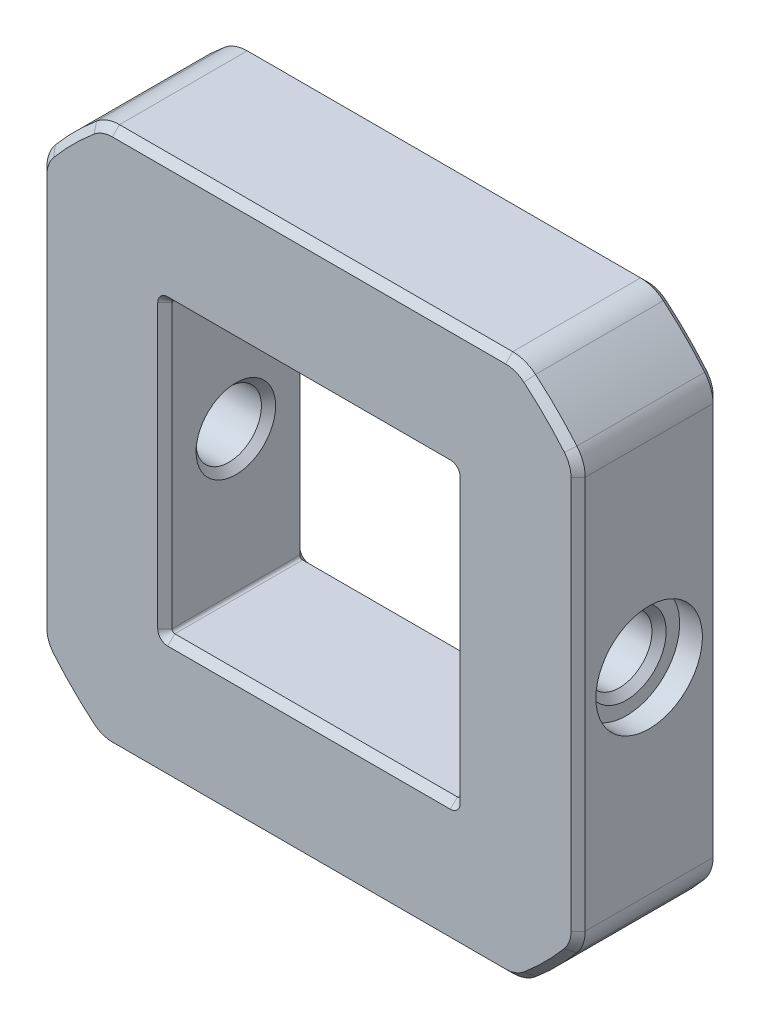
SolidWorks part; units mm, degrees
ref_plane "Front" through (0, 0, 0) normal (0, 0, 1) x (1, 0, 0)
ref_plane "Top" through (0, 0, 0) normal (0, 1, 0) x (1, 0, 0)
ref_plane "Right" through (0, 0, 0) normal (1, 0, 0) x (0, 0, -1)
sketch "Skizze1" plane through (0, 0, 0) normal (0, 0, 1) x (1, 0, 0)
  line L0 (14.7274, 18.95) -> (-14.7274, 18.95)
  line L1 (-10.15, -10.15) -> (10.15, -10.15)
  line L2 (-10.15, -10.15) -> (-10.15, 10.15)
  line L3 (-10.15, 10.15) -> (10.15, 10.15)
  line L4 (10.15, -10.15) -> (10.15, 10.15)
  line L5 (-10.15, -10.15) -> (10.15, 10.15) construction
  line L6 (-10.15, 10.15) -> (10.15, -10.15) construction
  line L7 (18.95, 14.7274) -> (18.95, -14.7274)
  line L8 (-14.7274, -18.95) -> (14.7274, -18.95)
  line L9 (-18.95, -14.7274) -> (-18.95, 14.7274)
  arc A0 (-18.95, -14.7274) -> (-14.7274, -18.95) centre (0, 0) ccw
  arc A1 (-14.7274, 18.95) -> (-18.95, 14.7274) centre (0, 0) ccw
  arc A2 (18.95, 14.7274) -> (14.7274, 18.95) centre (0, 0) ccw
  arc A3 (14.7274, -18.95) -> (18.95, -14.7274) centre (0, 0) ccw
  dimension "D1" = 48
  dimension "D2" = 20.3
  dimension "D3" = 37.9
extrude "Aufsatz-Linear austragen1" add sketch "Skizze1" along normal blind 10
fillet "Verrundung1" radius 0.2 4 edges at (10.15, -10.15, 5) (-10.15, -10.15, 5) (-10.15, 10.15, 5) (10.15, 10.15, 5)
fillet "Verrundung2" radius 2.5 8 edges at (14.7274, 18.95, 5) (18.95, 14.7274, 5) (18.95, -14.7274, 5) (14.7274, -18.95, 5) (-14.7274, -18.95, 5) (-18.95, -14.7274, 5) (-18.95, 14.7274, 5) (-14.7274, 18.95, 5)
sketch "Skizze2" plane through (18.95, 0, 0) normal (1, 0, 0) x (0, 0, -1)
  line L0 (0, 0) -> (-10, 0) construction
  line L1 (-10, -13.8437) -> (-10, 13.8437) construction
  circle A0 centre (-5, 0) radius 2.3
  dimension "D1" = 4.6
extrude "Schnitt-Linear austragen1" cut sketch "Skizze2" against normal through all
sketch "Sketch1" plane through (-18.95, 0, 0) normal (-1, 0, 0) x (0, 0, 1)
  circle A0 centre (5, 0) radius 3.75
  dimension "D1" = 7.5
extrude "Cut-Extrude1" cut sketch "Sketch1" against normal offset from surface (1.6 mm away) 7.2 up to face at (-10.15, 0, 2.7)
extrude "Cut-Extrude2" cut sketch "Sketch1<2>" along normal offset from surface (1.6 mm away) 7.2 from surface up to face at (10.15, 0, 7.3) starting at face at (18.95, 2.3, 5)
sketch "Sketch1<2>" plane through (-18.95, 0, 0) normal (-1, 0, 0) x (0, 0, 1) same geometry as "Sketch1"
chamfer "Fase2" distance 0.5 angle 45 52 edges at (10.15, 0, 7.3) (-10.15, 0, 2.7) (-10.0914, 10.0914, 10) (-10.15, 0, 10) (-10.0914, -10.0914, 10) (0, -10.15, 10) (10.0914, -10.0914, 10) (10.15, 0, 10) (10.0914, 10.0914, 10) (0, 10.15, 10) (18.7986, 14.7004, 10) (18.95, 0, 10) (18.7986, -14.7004, 10) (16.9706, -16.9706, 10) (14.7004, -18.7986, 10) (0, -18.95, 10) (-14.7004, -18.7986, 10) (-16.9706, -16.9706, 10) (-18.7986, -14.7004, 10) (-18.95, 0, 10) (-18.7986, 14.7004, 10) (-16.9706, 16.9706, 10) (-14.7004, 18.7986, 10) (0, 18.95, 10) (14.7004, 18.7986, 10) (16.9706, 16.9706, 10) (-10.0914, -10.0914, 0) (-10.15, 0, 0) (-10.0914, 10.0914, 0) (0, 10.15, 0) (10.0914, 10.0914, 0) (10.15, 0, 0) (10.0914, -10.0914, 0) (0, -10.15, 0) (-14.7004, 18.7986, 0) (-16.9706, 16.9706, 0) (-18.7986, 14.7004, 0) (-18.95, 0, 0) (-18.7986, -14.7004, 0) (-16.9706, -16.9706, 0) (-14.7004, -18.7986, 0) (0, -18.95, 0) (14.7004, -18.7986, 0) (16.9706, -16.9706, 0) (18.7986, -14.7004, 0) (18.95, 0, 0) (18.7986, 14.7004, 0) (16.9706, 16.9706, 0) (14.7004, 18.7986, 0) (0, 18.95, 0) (17.35, 0, 7.3) (-17.35, 0, 2.7)
